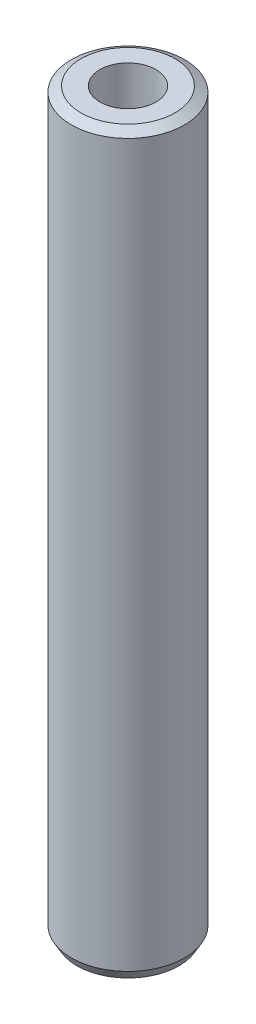
SolidWorks part; units mm, degrees
ref_plane "Front Plane" through (0, 0, 0) normal (0, 0, 1) x (1, 0, 0)
ref_plane "Top Plane" through (0, 0, 0) normal (0, 1, 0) x (1, 0, 0)
ref_plane "Right Plane" through (0, 0, 0) normal (1, 0, 0) x (0, 0, -1)
sketch "Sketch1" plane through (0, 0, 0) normal (0, 1, 0) x (1, 0, 0)
  circle A0 centre (0, 0) radius 40
  dimension "SHAFT_OD" = 80
extrude "Boss-Extrude1" add sketch "Sketch1" along normal blind 520.4181
sketch "Sketch2" plane through (0, 0, 0) normal (0, 1, 0) x (1, 0, 0)
  circle A0 centre (0, 0) radius 19.8319
  dimension "BORE_D" = 39.6639
extrude "Cut-Extrude1" cut sketch "Sketch2" along normal through all
chamfer "Chamfer1" distance 3.9283 angle 60 2 edges at (0, 520.4181, 40) (0, 0, 40) first distance on face at (0, 520.4181, 40) first distance on face at (0, 0, 19.8319)
